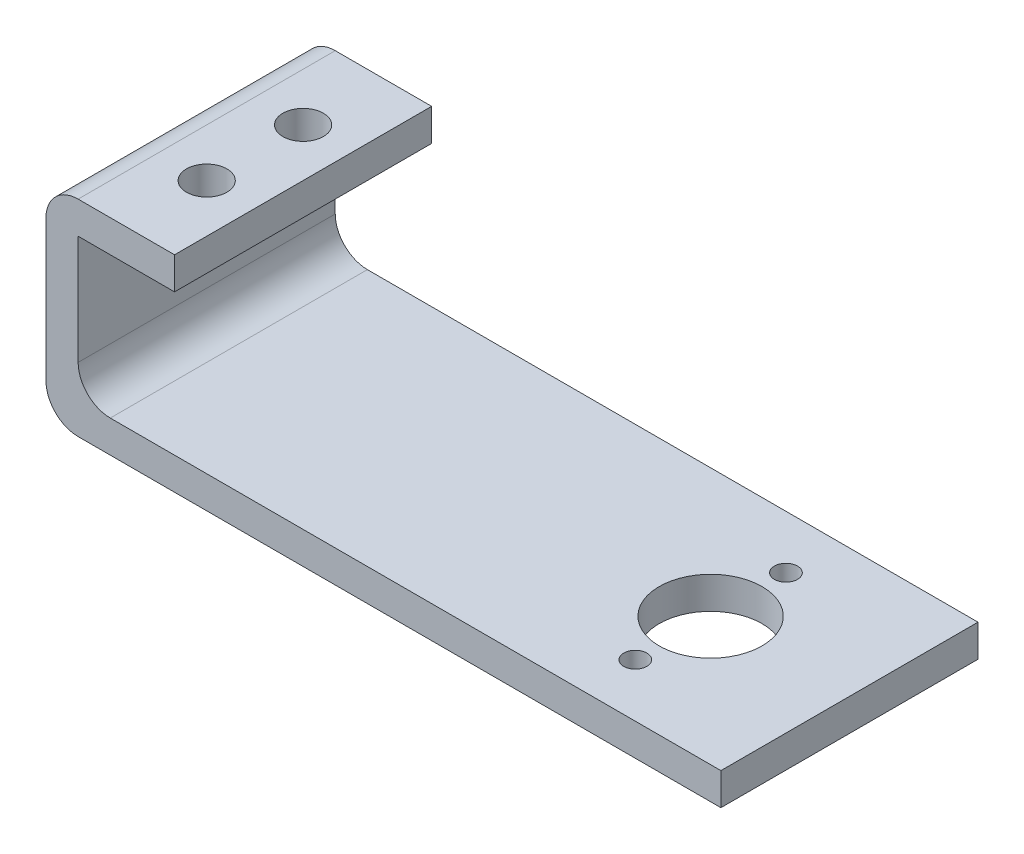
SolidWorks part; units mm, degrees
ref_plane "Front Plane" through (0, 0, 0) normal (0, 0, 1) x (1, 0, 0)
ref_plane "Top Plane" through (0, 0, 0) normal (0, 1, 0) x (1, 0, 0)
ref_plane "Right Plane" through (0, 0, 0) normal (1, 0, 0) x (0, 0, -1)
sketch "Sketch1" plane through (0, 0, 0) normal (0, 0, 1) x (1, 0, 0)
  line L0 (-17.0593, -16.2689) -> (-29.7593, -16.2689)
  line L1 (-29.7593, -16.2689) -> (-29.7593, -36.5889)
  line L2 (-29.7593, -36.5889) -> (36.9157, -36.5889)
  line L3 (-17.0593, -19.4439) -> (-26.5843, -19.4439)
  line L4 (-26.5843, -19.4439) -> (-26.5843, -33.4139)
  line L5 (-26.5843, -33.4139) -> (36.9157, -33.4139)
  line L6 (-17.0593, -16.2689) -> (-17.0593, -19.4439)
  line L7 (36.9157, -36.5889) -> (36.9157, -33.4139)
  line L8 (151.2157, -19.4439) -> (-26.5843, -19.4439) construction
  dimension "D2" = 12.7
  dimension "D3" = 13.97
  dimension "D4" = 63.5
  dimension "D1" = 3.175
extrude "Boss-Extrude1" add sketch "Sketch1" along normal blind 25.4
hole_wizard "Ø4.0mm Dowel Hole1" positions "Sketch6" profile "Sketch5" hole size "Ø4.0" standard "ANSI Metric" end condition up to next
sketch "Sketch6" plane through (0, -16.2689, 0) normal (0, 1, 0) x (1, 0, 0)
  line L1 (-17.0593, -25.4) -> (-17.0593, 0) construction
  line L2 (-17.0593, 0) -> (-29.7593, 0) construction
  point P0 (-21.8218, -7.9375)
  point P2 (-21.8218, -17.4625)
  dimension "D1" = 4.7625
  dimension "D2" = 9.525
  dimension "D3" = 7.9375
sketch "Sketch5" plane through (-21.8218, -16.2689, 7.9375) normal (1, 0, 0) x (0, 0, 1)
  line L0 (0, 0) -> (0, 3.175)
  line L1 (0, 3.175) -> (2, 3.175)
  line L2 (2, 3.175) -> (2, 0)
  line L5 (2, 0) -> (0, 0)
  line L11 (0, -6.35) -> (0, 107.95) construction
  dimension "Thru Hole Dia." = 4
  dimension "Thru Hole Depth" = 3.175
sketch "Sketch7" plane through (0, -36.5889, 0) normal (0, -1, 0) x (1, 0, 0)
  line L0 (-29.7593, 25.4) -> (36.9157, 25.4) construction
  line L2 (-26.5843, 25.4) -> (-26.5843, 0) construction
  circle A0 centre (23.1997, 12.7) radius 5.08
  circle A1 centre (23.1997, 12.7) radius 7.4422 construction
  circle A2 centre (23.1997, 5.2578) radius 1.143
  circle A3 centre (23.1997, 20.1422) radius 1.143
  dimension "D3" = 10.16
  dimension "D4" = 14.8844
  dimension "D5" = 2.286
  dimension "D1" = 12.7
  dimension "D2" = 49.784
extrude "Cut-Extrude1" cut sketch "Sketch7" against normal up to next
fillet "Fillet1" radius 3.175 3 edges at (-29.7593, -16.2689, 12.7) (-26.5843, -33.4139, 12.7) (-29.7593, -36.5889, 12.7)
